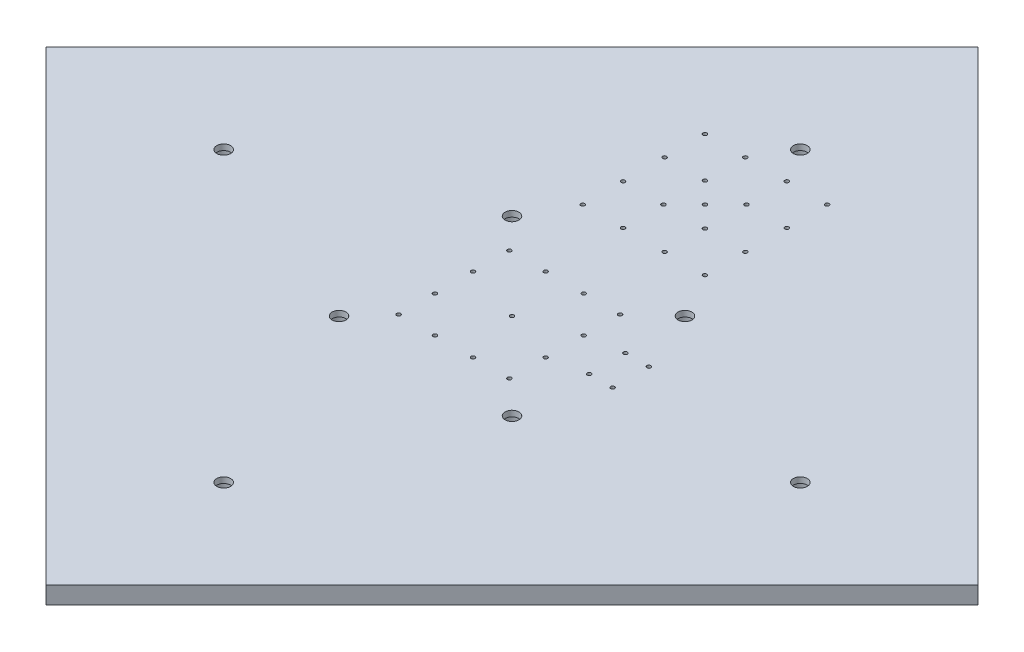
SolidWorks part; units mm, degrees
ref_plane "Front Plane" through (0, 0, 0) normal (0, 0, 1) x (1, 0, 0)
ref_plane "Top Plane" through (0, 0, 0) normal (0, 1, 0) x (1, 0, 0)
ref_plane "Right Plane" through (0, 0, 0) normal (1, 0, 0) x (0, 0, -1)
sketch "Sketch1" plane through (0, 0, 0) normal (0, 1, 0) x (1, 0, 0)
  line L0 (-404.1115, 0) -> (0, 404.1115)
  line L5 (-404.1115, 0) -> (0, -404.1115)
  line L6 (0, 404.1115) -> (404.1115, 0)
  line L7 (0, -404.1115) -> (404.1115, 0)
  line L8 (-404.1115, 0) -> (404.1115, 0) construction
  line L9 (0, 404.1115) -> (0, -404.1115) construction
  point P1 (0, 0)
  dimension "D1" = 571.5
extrude "Boss-Extrude1" add sketch "Sketch1" along normal blind 15
sketch "Extrusion Hole locations" plane through (0, 0, 0) normal (0, 1, 0) x (1, 0, 0)
  line L1 (75, -75) -> (-75, -75) construction
  line L2 (75, -75) -> (75, 75) construction
  line L3 (75, 75) -> (-75, 75) construction
  line L4 (-75, -75) -> (-75, 75) construction
  line L5 (75, -75) -> (-75, 75) construction
  line L6 (75, 75) -> (-75, -75) construction
  point P3 (0, 250)
  point P14 (250, 0)
  point P15 (0, -250)
  point P16 (-250, 0)
  point P105 (75, 75)
  point P108 (-75, 75)
  point P111 (-75, -75)
  point P114 (75, -75)
  dimension "D1" = 150
  dimension "D2" = 250
  dimension "D4" = 4
hole_wizard "CBORE for M10 SHCS1" positions "Extrusion Hole locations" profile "Sketch3" counterbore size "M10" standard "ANSI Metric" end condition through all
sketch "Sketch3" plane through (75, 0, 75) normal (1, 0, 0) x (0, 0, -1)
  line L0 (0, 0) -> (0, 15)
  line L1 (0, 15) -> (6, 15)
  line L3 (6, 15) -> (6, 10)
  line L4 (6, 10) -> (9, 10)
  line L5 (9, 10) -> (9, 0)
  line L7 (9, 0) -> (0, 0)
  line L11 (0, -6.35) -> (0, 107.95) construction
  dimension "Thru Hole Dia." = 12
  dimension "Thru Hole Depth" = 15
  dimension "C'Bore Dia." = 18
  dimension "C'Bore Depth" = 10
hole_wizard "CBORE for M3 SHCS1" positions "Sketch6" profile "Sketch7" counterbore size "M3" standard "ANSI Metric"
sketch "Sketch6" plane through (0, 0, 0) normal (0, -1, 0) x (-1, 0, 0)
  point P0 (0, 0)
  point P1 (0, 0)
  point P2 (-45.7, -48)
  point P3 (-45.7, -48)
  point P4 (18.8, -48)
  point P5 (-14.2, -48)
  point P6 (-14.2, -48)
  point P7 (50.3, -48)
  point P8 (50.3, -16.5)
  point P9 (50.3, 16.5)
  point P10 (50.3, 48)
  point P11 (18.8, 48)
  point P12 (-14.2, 48)
  point P13 (-45.7, 48)
  point P14 (0, 0)
  point P15 (0, 0)
  point P16 (-77.05, -10.1)
  point P17 (-97.4, -10.1)
  point P18 (-97.4, 21.3)
  point P19 (-77.05, 21.3)
  point P20 (-45.7, -16.5)
  point P21 (-45.7, 16.5)
sketch "Sketch7" plane through (0, 0, 0) normal (1, 0, 0) x (0, 0, -1)
  line L0 (0, 0) -> (0, 15)
  line L1 (0, 15) -> (1.7, 15)
  line L2 (1.7, 15) -> (1.7, 4)
  line L3 (1.7, 4) -> (3.25, 4)
  line L4 (3.25, 4) -> (3.25, 0)
  line L5 (3.25, 0) -> (0, 0)
  line L6 (0, -6.35) -> (0, 107.95) construction
  dimension "Thru Hole Dia." = 3.4
  dimension "Thru Hole Depth" = 15
  dimension "C'Bore Dia." = 6.5
  dimension "C'Bore Depth" = 4
hole_wizard "CBORE for M3 SHCS2" positions "Sketch8" profile "Sketch9" counterbore size "M3" standard "ANSI Metric"
sketch "Sketch8" plane through (0, 0, 0) normal (0, -1, 0) x (-1, 0, 0)
  point P0 (0, 167.3209)
  point P1 (0, 167.3209)
  point P2 (0, 167.3209)
  point P3 (53, 114.3209)
  point P4 (53, 149.3209)
  point P5 (53, 185.3209)
  point P6 (53, 220.3209)
  point P7 (18, 220.3209)
  point P8 (-18, 220.3209)
  point P9 (-53, 220.3209)
  point P10 (-53, 185.3209)
  point P11 (-53, 149.3209)
  point P12 (-53, 114.3209)
  point P13 (-18, 114.3209)
  point P14 (18, 114.3209)
  point P15 (18, 149.3209)
  point P16 (18, 185.3209)
  point P17 (-18, 149.3209)
  point P18 (-18, 185.3209)
sketch "Sketch9" plane through (0, 0, -167.3209) normal (1, 0, 0) x (0, 0, -1)
  line L0 (0, 0) -> (0, 15)
  line L1 (0, 15) -> (1.7, 15)
  line L2 (1.7, 15) -> (1.7, 4)
  line L3 (1.7, 4) -> (3.25, 4)
  line L4 (3.25, 4) -> (3.25, 0)
  line L5 (3.25, 0) -> (0, 0)
  line L6 (0, -6.35) -> (0, 107.95) construction
  dimension "Thru Hole Dia." = 3.4
  dimension "Thru Hole Depth" = 15
  dimension "C'Bore Dia." = 6.5
  dimension "C'Bore Depth" = 4
